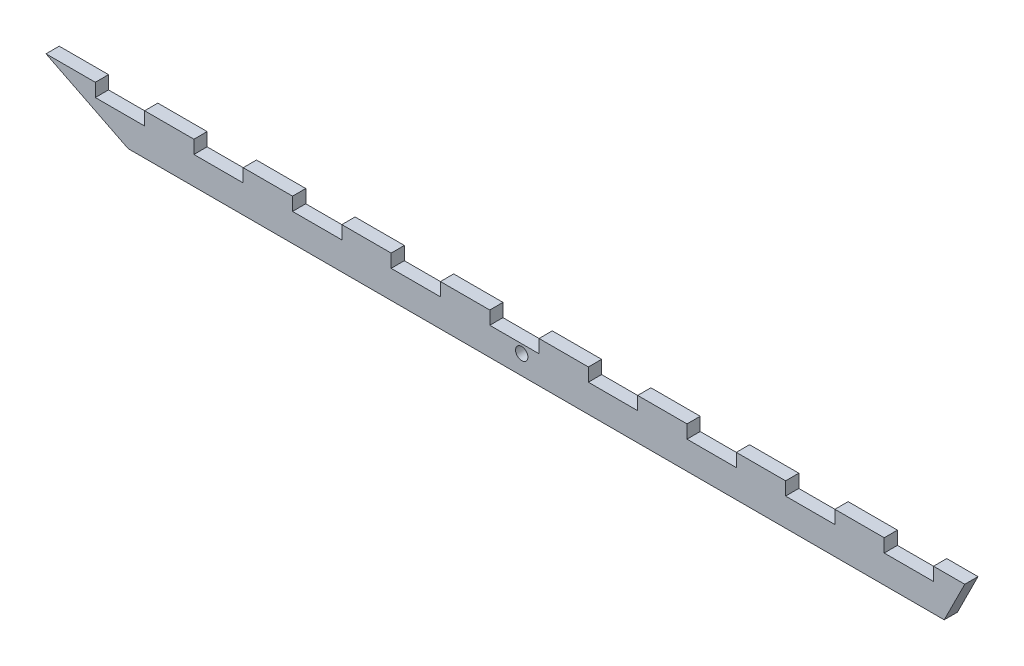
SolidWorks part; units mm, degrees
ref_plane "Front Plane" through (0, 0, 0) normal (0, 0, 1) x (1, 0, 0)
ref_plane "Top Plane" through (0, 0, 0) normal (0, 1, 0) x (1, 0, 0)
ref_plane "Right Plane" through (0, 0, 0) normal (1, 0, 0) x (0, 0, -1)
sketch "Sketch1" plane through (0, 0, 0) normal (0, 0, 1) x (1, 0, 0)
  line L0 (-95.7754, -4.7039) -> (-115.7754, 5.2961)
  line L3 (-95.7754, -4.7039) -> (102.8314, -4.7039)
  line L5 (-115.7754, 5.2961) -> (107.8314, 5.2961)
  line L6 (-95.7754, -4.7039) -> (107.8314, 5.2961) construction
  line L7 (102.8314, -4.7039) -> (107.8314, 5.2961)
  line L8 (102.8314, -4.7039) -> (-115.7754, 5.2961) construction
  circle A0 centre (0, 0) radius 1.5
  dimension "D5" = 3
  dimension "D1" = 26.565
  dimension "D2" = 223.6068
  dimension "D3" = 10
  dimension "D4" = 63.435
extrude "Boss-Extrude1" add sketch "Sketch1" along normal mid plane 3.22
sketch "Sketch2" plane through (0, 0, 1.61) normal (0, 0, 1) x (1, 0, 0)
  line L0 (107.8314, 5.2961) -> (-115.7754, 5.2961) construction
  line L1 (-103.7754, 5.2961) -> (-91.7754, 5.2961)
  line L2 (-103.7754, 5.2961) -> (-103.7754, 2.0761)
  line L3 (-103.7754, 2.0761) -> (-91.7754, 2.0761)
  line L4 (-91.7754, 5.2961) -> (-91.7754, 2.0761)
  line L5 (-115.7754, 5.2961) -> (-103.7754, 5.2961) construction
  dimension "D1" = 12
  dimension "D2" = 3.22
extrude "Cut-Extrude1" cut sketch "Sketch2" against normal up to next
pattern_linear "LPattern1" count 9 spacing 24 along (1, 0, 0) of "Cut-Extrude1"
equation "\"D1@Sketch1\"=atn(10/20)"
equation "\"D2@Sketch1\"=sqr(100^2+200^2)"
equation "\"D4@Sketch1\"=90-\"D1@Sketch1\""
equation "\"D3@LPattern1\"=2*\"D1@Sketch2\""
